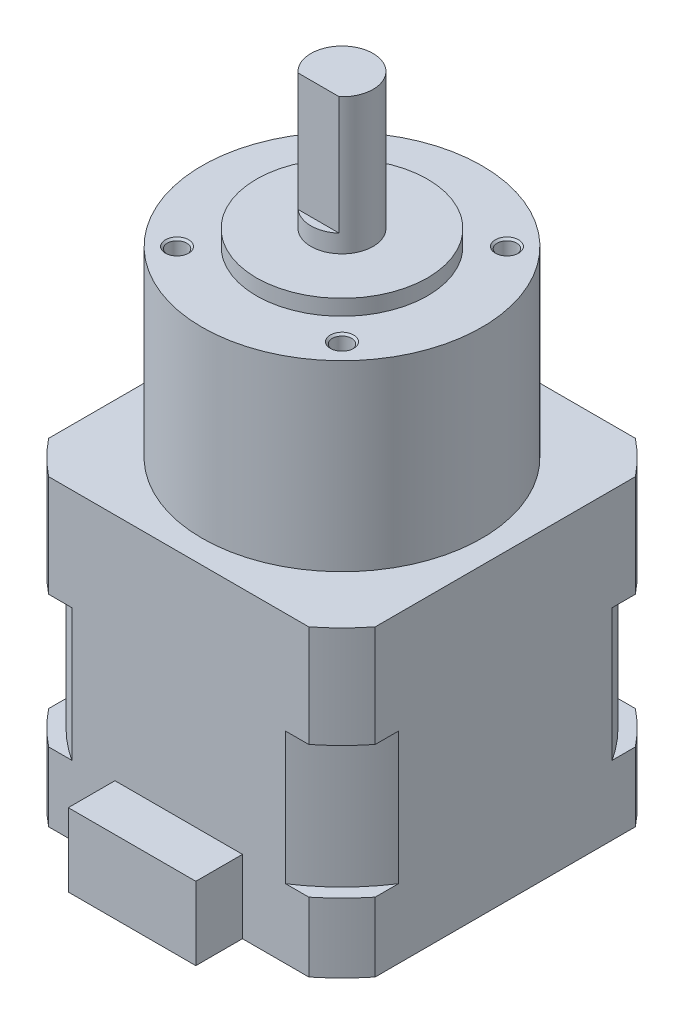
SolidWorks part; units mm, degrees
material "3.0505 (EN-AW 3105)"
ref_plane "Płaszczyzna przednia" through (0, 0, 0) normal (0, 0, 1) x (1, 0, 0)
ref_plane "Płaszczyzna górna" through (0, 0, 0) normal (0, 1, 0) x (1, 0, 0)
ref_plane "Płaszczyzna prawa" through (0, 0, 0) normal (1, 0, 0) x (0, 0, -1)
sketch "Szkic1" plane through (0, 0, 0) normal (0, 1, 0) x (1, 0, 0)
  line L0 (-2.6458, -3) -> (2.6458, -3)
  line L1 (-21, -21) -> (21, -21)
  line L2 (-21, -21) -> (-21, 21)
  line L3 (-21, 21) -> (21, 21)
  line L4 (21, -21) -> (21, 21)
  line L5 (-21, -21) -> (21, 21) construction
  line L6 (-21, 21) -> (21, -21) construction
  line L7 (0, 0) -> (0, 5.9906) construction
  circle A0 centre (0, 0) radius 18
  circle A1 centre (0, 0) radius 11
  circle A2 centre (0, 0) radius 4
  arc A3 (-2.6458, -3) -> (2.6458, -3) centre (0, 0) cw
  point P0 (0, 0)
  point P14 (0, 4)
  dimension "D2" = 36
  dimension "D3" = 22
  dimension "D4" = 8
  dimension "D1" = 42
  dimension "D5" = 7
extrude "Dodanie-wyciągnięcie1" add sketch "Szkic1" along normal blind 39 contours L4 L3 L2 L1
extrude "Dodanie-wyciągnięcie2" add sketch "Szkic1<3>" along normal blind 62.5 contours A0
sketch "Szkic1<3>" plane through (0, 0, 0) normal (0, 1, 0) x (1, 0, 0) same geometry as "Szkic1"
extrude "Dodanie-wyciągnięcie3" add sketch "Szkic1<4>" along normal blind 64.5 contours A1
sketch "Szkic1<4>" plane through (0, 0, 0) normal (0, 1, 0) x (1, 0, 0) same geometry as "Szkic1"
extrude "Dodanie-wyciągnięcie4" add sketch "Szkic1<5>" along normal blind 66.8 contours A2
sketch "Szkic1<5>" plane through (0, 0, 0) normal (0, 1, 0) x (1, 0, 0) same geometry as "Szkic1"
extrude "Dodanie-wyciągnięcie5" add sketch "Szkic1<6>" along normal blind 82 contours L0 A3
sketch "Szkic1<6>" plane through (0, 0, 0) normal (0, 1, 0) x (1, 0, 0) same geometry as "Szkic1"
sketch "Szkic2" plane through (0, 0, 0) normal (0, 1, 0) x (1, 0, 0)
  circle A0 centre (0, 0) radius 26.85
  dimension "D1" = 53.7
extrude "Wytnij-wyciągnięcie2" cut sketch "Szkic2" along normal through all flip side to cut
sketch "Szkic3" plane through (0, 0, 0) normal (0, 1, 0) x (1, 0, 0)
  circle A0 centre (0, 0) radius 25.1
  dimension "D1" = 50.2
extrude "Wytnij-wyciągnięcie3" cut sketch "Szkic3" along normal blind 17 from offset 8.9 flip side to cut
sketch "Szkic4" plane through (0, 0, 0) normal (0, 1, 0) x (1, 0, 0)
  circle A0 centre (0, 0) radius 4.65
  dimension "D1" = 9.3
extrude "Wytnij-wyciągnięcie5" cut sketch "Szkic4" along normal blind 4
sketch "Szkic5" plane through (0, 0, 0) normal (0, 1, 0) x (1, 0, 0)
  line L0 (0, 0) -> (-21.8173, 21.8173) construction
  line L1 (0, 0) -> (17.0567, 17.0567) construction
  line L2 (-16.7309, 21) -> (16.7309, 21) construction
  circle A0 centre (0, 0) radius 15 construction
  point P4 (-10.6066, 10.6066)
  point P8 (10.6066, 10.6066)
  point P9 (10.6066, -10.6066)
  point P10 (-10.6066, -10.6066)
  dimension "D1" = 30
  dimension "D2" = 45
hole_wizard "Otwór gwintowany M31" positions "Szkic6" profile "Szkic8" hole size "M3" standard "ISO"
sketch "Szkic6" plane through (0, 62.5, 0) normal (0, 1, 0) x (1, 0, 0)
  point P0 (-10.6066, 10.6066)
  point P3 (10.6066, 10.6066)
  point P6 (10.6066, -10.6066)
  point P9 (-10.6066, -10.6066)
sketch "Szkic8" plane through (-10.6066, 62.5, -10.6066) normal (1, 0, 0) x (0, 0, 1)
  line L0 (0, 0) -> (0, 9.7511)
  line L1 (0, 9.7511) -> (1.25, 9)
  line L2 (1.25, 9) -> (1.25, 0.25)
  line L3 (1.25, 0.25) -> (1.5, 0)
  line L5 (1.5, 0) -> (0, 0)
  line L6 (-1.25, 0.25) -> (-1.5, 0) construction
  line L10 (0, 9.7511) -> (-1.25, 9) construction
  line L11 (0, -6.35) -> (0, 107.95) construction
  dimension "Średnica otworu" = 2.5
  dimension "Głębokośc otworu" = 9
  dimension "Średnica zewnętrznego pogłębienia stożkowego" = 3
  dimension "Kąt zewnętrznego pogłębienia stożkowego" = 90
  dimension "Kąt wiertła" = 118
sketch "Szkic18" plane through (0, 0, 0) normal (0, 0, 1) x (1, 0, 0)
  line L0 (15, 0) -> (-15, 0) construction
  line L1 (-8.2, 0) -> (8.2, 0)
  line L2 (-8.2, 0) -> (-8.2, 9.4)
  line L3 (-8.2, 9.4) -> (8.2, 9.4)
  line L4 (8.2, 0) -> (8.2, 9.4)
  dimension "D1" = 9.4
  dimension "D2" = 16.4
  dimension "D3" = 8.2
extrude "Dodanie-wyciągnięcie6" add sketch "Szkic18" along normal blind 6 from surface starting at face at (0, 18.1, 21)
equation "\"D3@Szkic18\"=\"D2@Szkic18\"/2"
